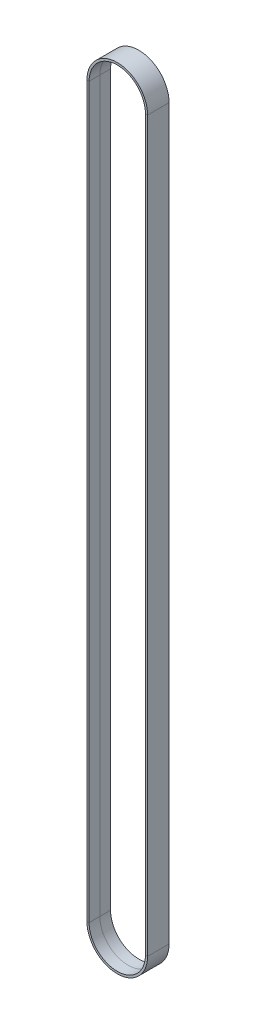
SolidWorks part; units mm, degrees
ref_plane "Спереди" through (0, 0, 0) normal (0, 0, 1) x (1, 0, 0)
ref_plane "Сверху" through (0, 0, 0) normal (0, 1, 0) x (1, 0, 0)
ref_plane "Справа" through (0, 0, 0) normal (1, 0, 0) x (0, 0, -1)
sketch "Эскиз2" plane through (0, 0, 0) normal (0, 0, 1) x (1, 0, 0)
  line L0 (0, 0) -> (1, 0) construction
  line L1 (0, 0) -> (0, 1) construction
  line L2 (26.25, 0) -> (26.25, -678.6787)
  line L3 (-26.25, -678.6787) -> (-26.25, 0)
  arc A0 (-26.25, 0) -> (26.25, 0) centre (0, 0) cw
  arc A1 (26.25, -678.6787) -> (-26.25, -678.6787) centre (0, -678.6787) cw
ref_plane "Плоскость1" through (0, 0, 0) normal (0, 0, 1) x (1, 0, 0)
sketch "Эскиз3" plane through (0, 0, 0) normal (0, 0, 1) x (1, 0, 0)
  line L0 (-26.25, -678.6787) -> (-26.25, 0) construction
  line L1 (26.25, 0) -> (26.25, -678.6787) construction
  line L2 (-26.25, -678.6787) -> (-26.25, 0)
  line L3 (26.25, 0) -> (26.25, -678.6787)
  arc A0 (-26.25, -678.6787) -> (26.25, -678.6787) centre (0, -678.6787) ccw construction
  arc A1 (26.25, 0) -> (-26.25, 0) centre (0, 0) ccw construction
  arc A2 (-26.25, -678.6787) -> (26.25, -678.6787) centre (0, -678.6787) ccw
  arc A3 (26.25, 0) -> (-26.25, 0) centre (0, 0) ccw
ref_plane "Плоскость2" through (0, 0, 0) normal (0, 1, 0) x (1, 0, 0)
sketch "Эскиз4" plane through (0, 0, 0) normal (0, 1, 0) x (1, 0, 0)
  line L0 (-2.8281, -10) -> (-4.4908, -10) construction
  line L2 (-26.25, 0) -> (-26.25, -10)
  line L3 (-26.25, -10) -> (-28.25, -10)
  line L5 (-4.4908, 10) -> (-2.8281, 10) construction
  line L11 (-26.25, 0) -> (-26.25, 10)
  line L12 (-26.25, 10) -> (-28.25, 10)
  line L14 (-28.25, 10) -> (-28.25, -10)
  dimension "D1" = 2
  dimension "D2" = 2
sweep "По траектории1" add profiles "Эскиз4" path "Эскиз3"
